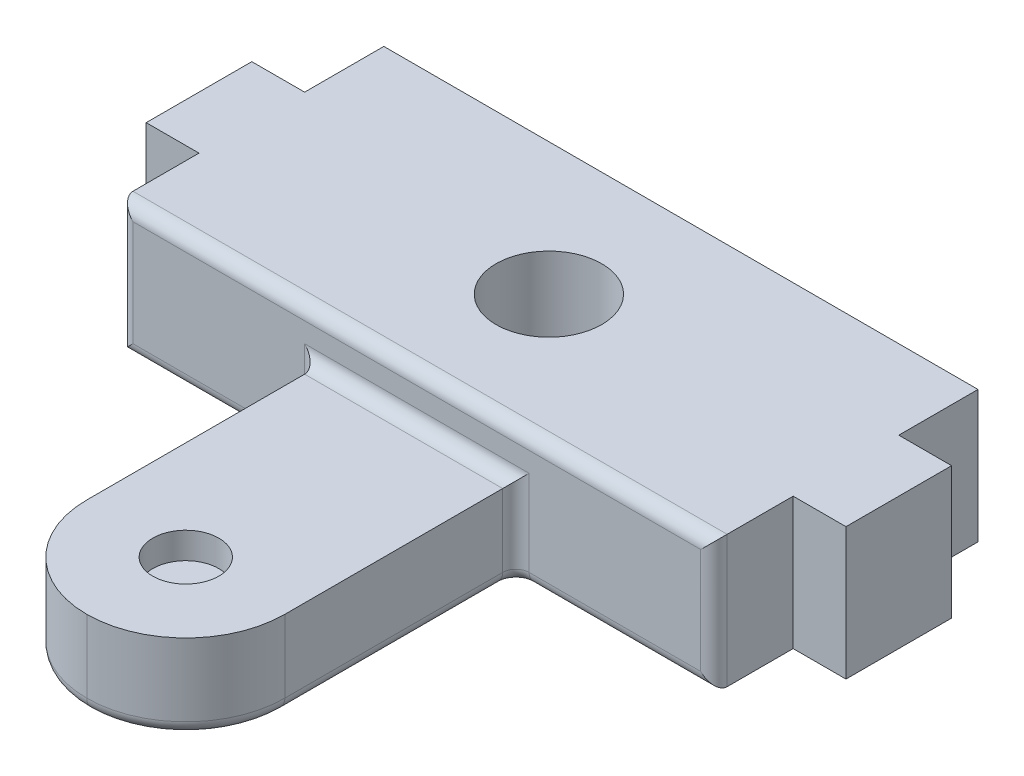
SolidWorks part; units mm, degrees
material "6061-T6 (SS)"
ref_plane "Ebene vorne" through (0, 0, 0) normal (0, 0, 1) x (1, 0, 0)
ref_plane "Ebene oben" through (0, 0, 0) normal (0, 1, 0) x (1, 0, 0)
ref_plane "Ebene rechts" through (0, 0, 0) normal (1, 0, 0) x (0, 0, -1)
sketch "Skizze3" plane through (0, 0, 0) normal (0, 1, 0) x (1, 0, 0)
  line L0 (-265, -40) -> (-265, 40)
  line L1 (-265, 40) -> (-225, 40)
  line L2 (-225, 40) -> (-225, 100)
  line L3 (-225, 100) -> (225, 100)
  line L4 (0, 100) -> (0, 0) construction
  line L5 (0, 0) -> (-265, 0) construction
  line L6 (-225, -100) -> (225, -100)
  line L7 (-225, -40) -> (-225, -100)
  line L8 (-265, -40) -> (-225, -40)
  line L9 (265, -40) -> (225, -40)
  line L10 (225, -40) -> (225, -100)
  line L11 (225, 40) -> (225, 100)
  line L12 (265, 40) -> (225, 40)
  line L13 (265, -40) -> (265, 40)
  point P14 (0, -100)
  dimension "D1" = 40
  dimension "D2" = 40
  dimension "D3" = 225
  dimension "D4" = 60
extrude "Aufsatz-Linear austragen1" add sketch "Skizze3" along normal blind 50 and the other way blind 50
sketch "Skizze4" plane through (0, 50, 0) normal (0, 1, 0) x (1, 0, 0)
  circle A0 centre (0, 0) radius 40
  dimension "D1" = 80
extrude "Schnitt-Linear austragen1" cut sketch "Skizze4" against normal up to surface (100 mm away) up to face at (0, -50, 0)
sketch "Skizze5" plane through (0, 0, 100) normal (0, 0, 1) x (1, 0, 0)
  line L0 (-225, -50) -> (225, -50) construction
  line L1 (-75, -50) -> (75, -50)
  line L2 (-75, -50) -> (-75, 50)
  line L3 (-75, 50) -> (75, 50)
  line L4 (75, -50) -> (75, 50)
  line L5 (-225, 50) -> (225, 50) construction
  point P8 (0, 50)
  dimension "D1" = 150
extrude "Aufsatz-Linear austragen2" add sketch "Skizze5" along normal blind 250
fillet "Verrundung2" radius 75 2 edges at (-75, 0, 350) (75, 0, 350)
ref_plane "Ebene1" through (0, 50, 350) normal (0, 1, 0) x (1, 0, 0)
sketch "Skizze8" plane through (75, 0, 0) normal (1, 0, 0) x (0, 0, -1)
  line L1 (-350, 50) -> (-230, 50)
  line L2 (-350, 50) -> (-350, 15)
  line L3 (-350, 15) -> (-230, 15)
  line L4 (-230, 50) -> (-230, 15)
  dimension "D1" = 120
  dimension "D2" = 35
extrude "Schnitt-Linear austragen3" cut sketch "Skizze8" against normal up to surface (150 mm away) up to face at (-75, 0, 187.5)
sketch "Skizze9" plane through (0, 15, 0) normal (0, 1, 0) x (1, 0, 0)
  circle A0 centre (0, -275) radius 25
  dimension "D1" = 50
extrude "Schnitt-Linear austragen4" cut sketch "Skizze9" against normal blind 20
sketch "Skizze10" plane through (0, 50, 0) normal (0, 1, 0) x (1, 0, 0)
  line L1 (-75, -230) -> (75, -230)
  line L2 (-75, -230) -> (-75, -100)
  line L3 (-75, -100) -> (75, -100)
  line L4 (75, -230) -> (75, -100)
extrude "Schnitt-Linear austragen5" cut sketch "Skizze10" against normal up to surface (35 mm away) up to face at (-25, 15, 275)
fillet "Verrundung3" radius 10 12 edges at (-53.033, -50, 328.033) (53.033, -50, 328.033) (-75, -50, 187.5) (75, -50, 187.5) (0, 15, 100) (-75, -17.5, 100) (-150, -50, 100) (-225, 0, 100) (0, 50, 100) (225, 0, 100) (150, -50, 100) (75, -17.5, 100)
